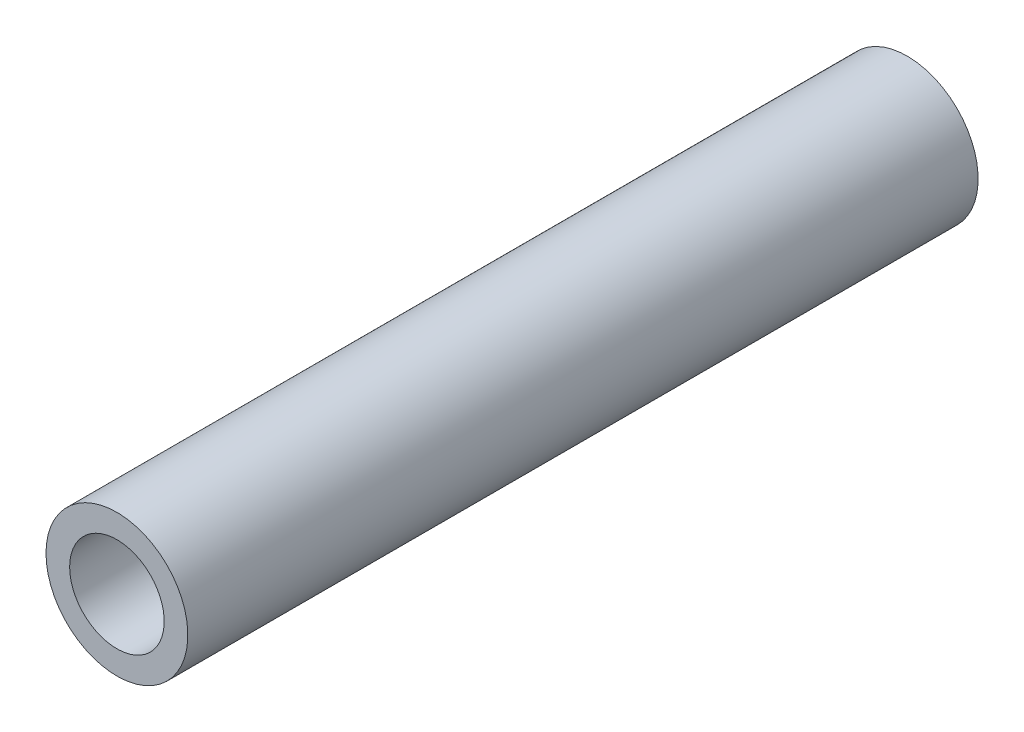
SolidWorks part; units mm, degrees
material "C-Fibra di vetro"
ref_plane "Piano frontale" through (0, 0, 0) normal (0, 0, 1) x (1, 0, 0)
ref_plane "Piano superiore" through (0, 0, 0) normal (0, 1, 0) x (1, 0, 0)
ref_plane "Piano destro" through (0, 0, 0) normal (1, 0, 0) x (0, 0, -1)
sketch "Schizzo1" plane through (0, 0, 0) normal (0, 0, 1) x (1, 0, 0)
  circle A0 centre (215, -26.4239) radius 3
  circle A1 centre (215, -26.4239) radius 2
  dimension "D1" = 1
  dimension "D2" = 6
extrude "Estrusione-Estrusione1" add sketch "Schizzo1" along normal up to surface (33.4279 mm away)
